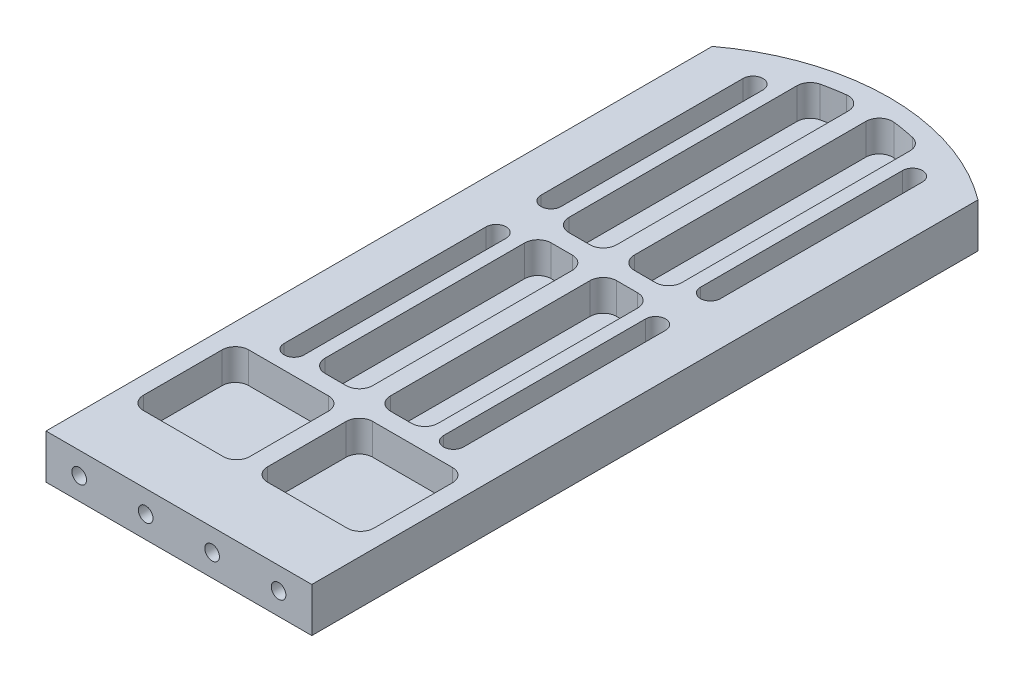
SolidWorks part; units mm, degrees
material "3.1355 (EN-AW 2024)"
ref_plane "Front" through (0, 0, 0) normal (0, 0, 1) x (1, 0, 0)
ref_plane "Top" through (0, 0, 0) normal (0, 1, 0) x (1, 0, 0)
ref_plane "Right" through (0, 0, 0) normal (1, 0, 0) x (0, 0, -1)
sketch "Эскиз1" plane through (0, 0, 0) normal (0, 1, 0) x (1, 0, 0)
  line L0 (12, 147.6) -> (12, 102) construction
  line L1 (48, 147.6) -> (48, 102) construction
  line L2 (12, 147.6) -> (12, 102) construction
  line L3 (14.25, 147.6) -> (14.25, 102)
  line L4 (9.75, 147.6) -> (9.75, 102)
  line L5 (48, 147.6) -> (48, 102) construction
  line L6 (50.25, 147.6) -> (50.25, 102)
  line L7 (45.75, 147.6) -> (45.75, 102)
  line L8 (0, 0) -> (0, 150.3845)
  line L9 (60, 0) -> (60, 150.3845)
  line L10 (12, 147.6) -> (48, 147.6) construction
  line L11 (0, 0) -> (60, 0)
  line L13 (12, 89.6) -> (12, 44) construction
  line L14 (14.25, 89.6) -> (14.25, 44)
  line L15 (9.75, 89.6) -> (9.75, 44)
  line L16 (30, 0) -> (30, 160.3845) construction
  line L17 (48, 89.6) -> (48, 44) construction
  line L18 (45.75, 89.6) -> (45.75, 44)
  line L19 (50.25, 89.6) -> (50.25, 44)
  arc A0 (14.25, 147.6) -> (9.75, 147.6) centre (12, 147.6) ccw
  arc A1 (9.75, 102) -> (14.25, 102) centre (12, 102) ccw
  arc A2 (50.25, 147.6) -> (45.75, 147.6) centre (48, 147.6) ccw
  arc A3 (45.75, 102) -> (50.25, 102) centre (48, 102) ccw
  arc A4 (0, 150.3845) -> (60, 150.3845) centre (30, 110.3845) cw
  arc A5 (14.25, 89.6) -> (9.75, 89.6) centre (12, 89.6) ccw
  arc A6 (9.75, 44) -> (14.25, 44) centre (12, 44) ccw
  arc A7 (45.75, 89.6) -> (50.25, 89.6) centre (48, 89.6) cw
  arc A8 (50.25, 44) -> (45.75, 44) centre (48, 44) cw
  point P4 (12, 124.8)
  point P9 (48, 124.8)
  point P26 (12, 66.8)
  point P35 (48, 66.8)
  dimension "D4" = 4.5
  dimension "D7" = 50
  dimension "D8" = 44
  dimension "D1" = 45.6
  dimension "D2" = 36
  dimension "D3" = 4.5
  dimension "D5" = 58
  dimension "D6" = 60
  dimension "D9" = 12
  dimension "D10" = 41.34
  dimension "D12" = 4.5
  dimension "D13" = 45.6
extrude "Бобышка-Вытянуть1" add sketch "Эскиз1" along normal blind 10
sketch "Эскиз2" plane through (0, 10, 0) normal (0, 1, 0) x (1, 0, 0)
  line L0 (4, 15) -> (28, 15)
  line L3 (0, 0) -> (60, 0) construction
  line L4 (30, 160.3845) -> (30, 15) construction
  line L5 (28, 156.341) -> (28, 15)
  line L6 (56, 15) -> (32, 15)
  line L7 (56, 38.75) -> (56, 15)
  line L8 (48, 38.75) -> (56, 38.75)
  line L9 (28, 160.3845) -> (28, 15) construction
  line L30 (17.25, 102) -> (17.25, 147.6)
  line L31 (6.75, 147.6) -> (6.75, 102)
  line L32 (17.25, 44) -> (17.25, 154.5822)
  line L33 (6.75, 150.0763) -> (6.75, 44) construction
  line L36 (6.75, 89.6) -> (6.75, 44)
  line L37 (17.25, 44) -> (17.25, 89.6)
  line L38 (12, 38.75) -> (4, 38.75)
  line L39 (4, 150.3845) -> (4, 0)
  line L40 (4, 38.75) -> (4, 15)
  line L41 (42.75, 44) -> (42.75, 154.5822)
  line L42 (32, 156.341) -> (32, 15)
  arc A0 (60, 150.3845) -> (0, 150.3845) centre (30, 110.3845) ccw construction
  arc A1 (48, 38.75) -> (42.75, 44) centre (48, 44) cw
  arc A2 (32, 156.341) -> (42.75, 154.5822) centre (30, 110.3845) cw
  arc A23 (6.75, 102) -> (17.25, 102) centre (12, 102) ccw
  arc A24 (17.25, 147.6) -> (6.75, 147.6) centre (12, 147.6) ccw
  arc A25 (28, 156.341) -> (17.25, 154.5822) centre (30, 110.3845) ccw
  arc A29 (6.75, 44) -> (17.25, 44) centre (12, 44) ccw
  arc A30 (17.25, 89.6) -> (6.75, 89.6) centre (12, 89.6) ccw
  arc A31 (12, 38.75) -> (17.25, 44) centre (12, 44) ccw
  point P15 (32, 160.3845)
  point P20 (28.16, 156.3477)
  point P21 (2.4, 147.1845)
  point P36 (30, 158.245)
  dimension "D1" = 15
  dimension "D2" = 3
  dimension "D3" = 3
  dimension "D4" = 4
extrude "Вырез-Вытянуть1" cut sketch "Эскиз2" against normal blind 7
sketch "Эскиз3" plane through (0, 10, 0) normal (0, 1, 0) x (1, 0, 0)
  line L0 (12, 38.75) -> (48, 38.75)
  line L1 (17.099, 42.75) -> (42.901, 42.75)
  line L2 (12, 38.75) -> (17.099, 42.75)
  line L3 (12, 42.75) -> (48, 42.75) construction
  line L4 (42.901, 42.75) -> (48, 38.75)
  line L5 (12, 99.75) -> (12, 91.85) construction
  line L6 (12, 95.8) -> (48, 95.8) construction
  line L7 (17.25, 93.8) -> (42.75, 93.8)
  line L8 (17.25, 97.8) -> (42.75, 97.8)
  line L9 (17.25, 154.5822) -> (17.25, 44) construction
  line L10 (42.75, 44) -> (42.75, 154.5822) construction
  line L11 (17.25, 97.8) -> (17.25, 93.8)
  line L12 (42.75, 93.8) -> (42.75, 97.8)
  line L14 (12, 97.8) -> (48, 97.8) construction
  line L15 (12, 93.8) -> (48, 93.8) construction
  arc A1 (9.75, 102) -> (14.25, 102) centre (12, 102) ccw construction
  arc A2 (14.25, 89.6) -> (9.75, 89.6) centre (12, 89.6) ccw construction
extrude "Бобышка-Вытянуть2" add sketch "Эскиз3" against normal up to next (10 mm away)
fillet "Скругление1" radius 3 24 edges at (32, 6.5, -38.75) (56, 6.5, -38.75) (56, 6.5, -15) (32, 6.5, -15) (4, 6.5, -15) (28, 6.5, -15) (28, 6.5, -38.75) (4, 6.5, -38.75) (17.25, 6.5, -93.8) (28, 6.5, -93.8) (17.099, 6.5, -42.75) (28, 6.5, -42.75) (32, 6.5, -42.75) (42.901, 6.5, -42.75) (42.75, 6.5, -93.8) (32, 6.5, -93.8) (32, 6.5, -156.341) (42.75, 6.5, -154.5822) (42.75, 6.5, -97.8) (32, 6.5, -97.8) (17.25, 6.5, -97.8) (28, 6.5, -97.8) (17.25, 6.5, -154.5822) (28, 6.5, -156.341)
sketch "Эскиз4" plane through (0, 0, 0) normal (0, 0, 1) x (1, 0, 0)
  line L0 (0, 5) -> (7.5, 5) construction
  line L1 (0, 10) -> (0, 0) construction
  line L2 (7.5, 5) -> (22.5, 5) construction
  line L3 (22.5, 5) -> (37.5, 5) construction
  line L4 (37.5, 5) -> (52.5, 5) construction
  dimension "D1" = 7.5
  dimension "D2" = 15
  dimension "D3" = 15
  dimension "D4" = 15
hole_wizard "Отверстие обработанное метчиком M4x0.71" positions "Эскиз8" profile "Эскиз7" tap size "M4x0.7" standard "Ansi Metric" end condition up to next
sketch "Эскиз8" plane through (0, 0, 0) normal (0, 0, 1) x (1, 0, 0)
  point P0 (7.5, 5)
  point P3 (22.5, 5)
  point P6 (37.5, 5)
  point P9 (52.5, 5)
sketch "Эскиз7" plane through (7.5, 5, 0) normal (1, 0, 0) x (0, -1, 0)
  line L0 (0, 0) -> (0, 15)
  line L1 (0, 15) -> (1.65, 15)
  line L2 (1.65, 15) -> (1.65, 0)
  line L5 (1.65, 0) -> (0, 0)
  line L11 (0, -6.35) -> (0, 107.95) construction
  dimension "Диаметр проходного сверла" = 3.3
  dimension "Глубина проходного сверла" = 15
cosmetic thread "Отверстие резьбы1" parameters "D2"=4
cosmetic thread "Отверстие резьбы2" parameters "D2"=4
cosmetic thread "Отверстие резьбы3" parameters "D2"=4
cosmetic thread "Отверстие резьбы4" parameters "D2"=4
equation "\"D4@Эскиз1\"=\"D3@Эскиз1\""
equation "\"D12@Эскиз1\"=\"D3@Эскиз1\""
equation "\"D13@Эскиз1\"=\"D1@Эскиз1\""
